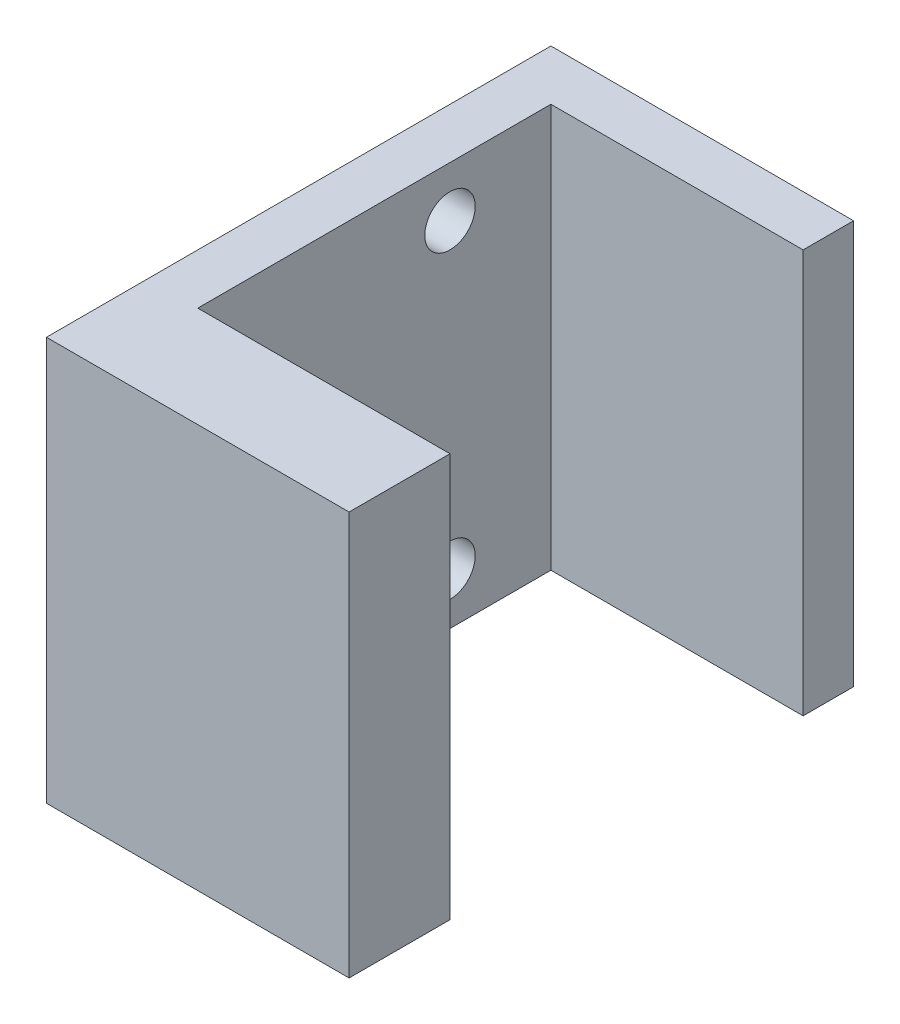
SolidWorks part; units mm, degrees
ref_plane "Front Plane" through (0, 0, 0) normal (0, 0, 1) x (1, 0, 0)
ref_plane "Top Plane" through (0, 0, 0) normal (0, 1, 0) x (1, 0, 0)
ref_plane "Right Plane" through (0, 0, 0) normal (1, 0, 0) x (0, 0, -1)
sketch "Sketch1" plane through (0, 0, 0) normal (0, 1, 0) x (1, 0, 0)
  line L0 (0, 225) -> (0, 250)
  line L1 (0, 0) -> (-150, 0)
  line L2 (0, 0) -> (0, 50)
  line L3 (0, 250) -> (-150, 250)
  line L4 (-150, 0) -> (-150, 250)
  line L5 (0, 50) -> (-125, 50)
  line L7 (0, 225) -> (-125, 225)
  line L8 (-125, 50) -> (-125, 225)
  dimension "D1" = 25
  dimension "D2" = 50
  dimension "D3" = 25
  dimension "D4" = 250
  dimension "D5" = 150
extrude "Boss-Extrude1" add sketch "Sketch1" along normal blind 200
sketch "Sketch2" plane through (-150, 0, 0) normal (-1, 0, 0) x (0, 0, 1)
  line L0 (-175, 175) -> (-175, 25) construction
  line L1 (-250, 200) -> (-250, 0) construction
  point P4 (-250, 100)
  point P5 (-175, 100)
  dimension "D1" = 75
  dimension "D2" = 150
hole_wizard "Hole1" positions "3DSketch1" profile "Sketch3" legacy end condition through all
sketch3d "3DSketch1"
  point P0 (-150, 175, -175)
  point P3 (-150, 25, -175)
sketch "Sketch3" plane through (-150, 175, -175) normal (0, 1, 0) x (0, 0, 1)
  line L0 (0, 0) -> (0, 150)
  line L1 (0, 150) -> (12.5, 150)
  line L2 (12.5, 150) -> (12.5, 0)
  line L3 (12.5, 0) -> (0, 0)
  line L4 (0, 110) -> (0, -10) construction
  dimension "Diameter" = 25
  dimension "Depth" = 150
